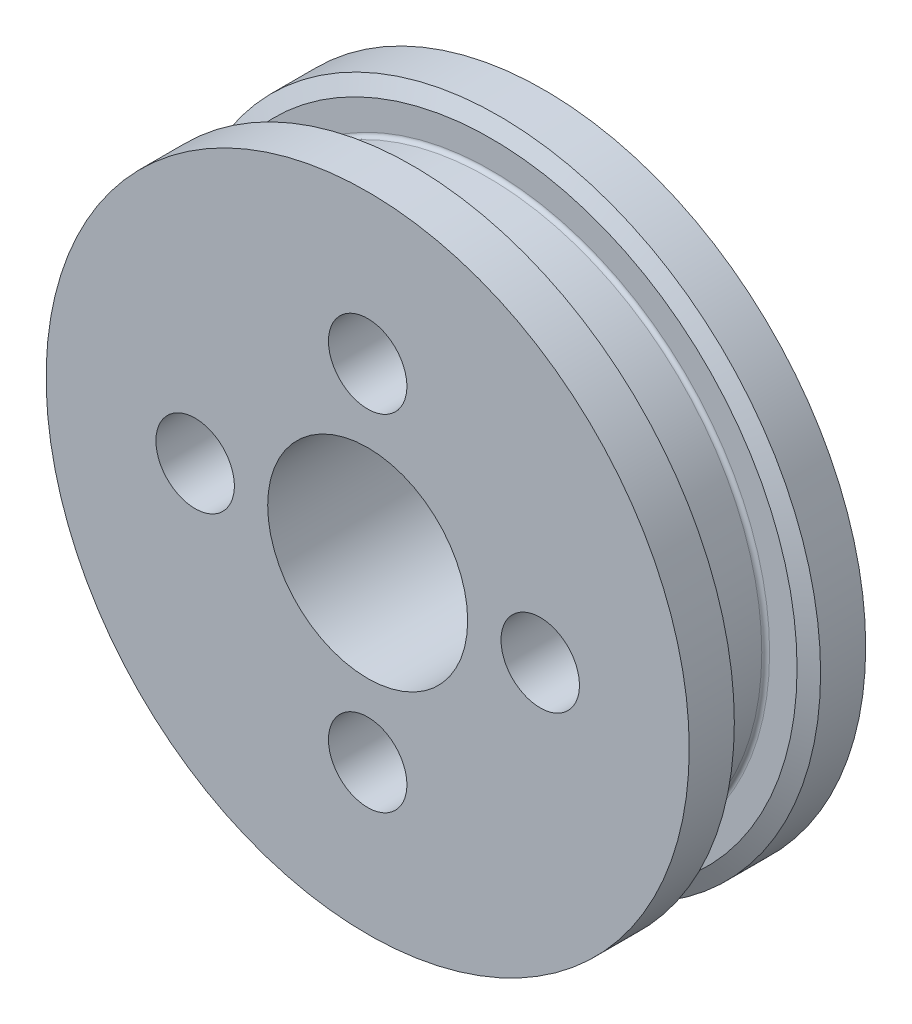
SolidWorks part; units mm, degrees
ref_plane "Front Plane" through (0, 0, 0) normal (0, 0, 1) x (1, 0, 0)
ref_plane "Top Plane" through (0, 0, 0) normal (0, 1, 0) x (1, 0, 0)
ref_plane "Right Plane" through (0, 0, 0) normal (1, 0, 0) x (0, 0, -1)
sketch "Sketch2" plane through (0, 0, 0) normal (1, 0, 0) x (0, 0, -1)
  line L0 (0, 6.477) -> (0, 20.828)
  line L1 (0, 20.828) -> (2.921, 20.828)
  line L2 (3.429, 19.812) -> (3.429, 17.78)
  line L3 (3.429, 17.78) -> (8.001, 17.78)
  line L4 (8.001, 17.78) -> (8.001, 19.812)
  line L5 (8.509, 20.828) -> (11.43, 20.828)
  line L6 (11.43, 20.828) -> (11.43, 6.477)
  line L8 (0, 6.477) -> (11.43, 6.477)
  line L9 (0, 6.477) -> (0, 0) construction
  line L10 (0, 0) -> (10.7816, 0) construction
  line L11 (8.001, 19.812) -> (8.509, 20.828)
  line L12 (2.921, 20.828) -> (3.429, 19.812)
  point P4 (3.429, 20.828)
  point P7 (8.001, 20.828)
  dimension "D1" = 17.78
  dimension "D2" = 11.43
  dimension "D3" = 3.048
  dimension "D4" = 6.477
  dimension "D5" = 4.572
  dimension "D6" = 1.016
  dimension "D7" = 0.508
  dimension "D8" = 0.508
  dimension "D9" = 1.016
revolve "Revolve1" add sketch "Sketch2" angle 360 about L10
sketch "Sketch3" plane through (0, 0, -11.43) normal (0, 0, -1) x (-1, 0, 0)
  line L1 (-8.255, -8.255) -> (8.255, -8.255)
  line L2 (-8.255, -8.255) -> (-8.255, 8.255)
  line L3 (-8.255, 8.255) -> (8.255, 8.255)
  line L4 (8.255, -8.255) -> (8.255, 8.255)
  circle A0 centre (0, 0) radius 6.477 construction
  circle A1 centre (0, 0) radius 6.477
  point P4 (8.255, 0)
  point P6 (0, 8.255)
  dimension "D1" = 16.51
extrude "Boss-Extrude1" add sketch "Sketch3" along normal blind 3.175
ref_plane "Plane1" through (0, 0, -5.715) normal (0, 0, -1) x (-1, 0, 0)
sketch "Sketch4" plane through (0, 0, -11.43) normal (0, 0, -1) x (-1, 0, 0)
  line L0 (0, 11.176) -> (0, 0) construction
  line L1 (0, 0) -> (0, -11.176) construction
  line L2 (-11.176, 0) -> (0, 0) construction
  line L3 (0, 0) -> (11.176, 0) construction
  circle A0 centre (0, 11.176) radius 2.54
  circle A1 centre (11.176, 0) radius 2.54
  circle A2 centre (0, -11.176) radius 2.54
  circle A3 centre (-11.176, 0) radius 2.54
  dimension "D1" = 5.08
  dimension "D2" = 11.176
extrude "Cut-Extrude1" cut sketch "Sketch4" against normal through all both and the other way through all
fillet "Fillet1" radius 0.254 2 edges at (17.78, 0, -8.001) (17.78, 0, -3.429)
